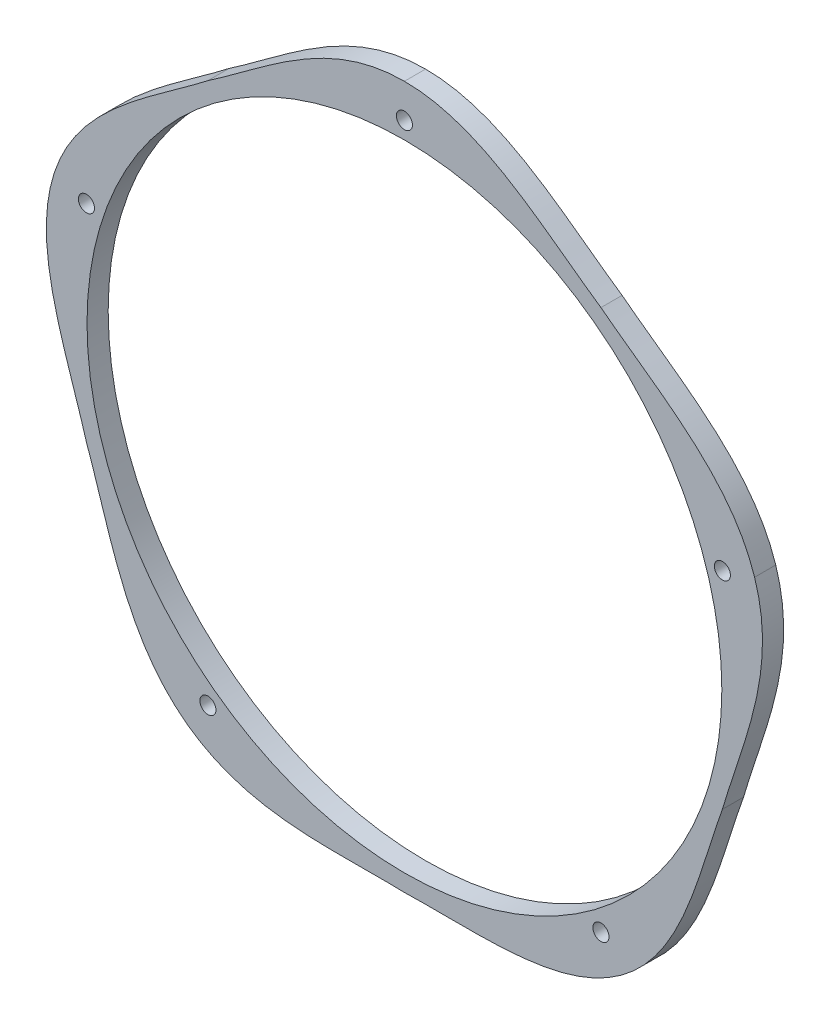
SolidWorks part; units mm, degrees
material "ABS"
ref_plane "Płaszczyzna przednia" through (0, 0, 0) normal (0, 0, 1) x (1, 0, 0)
ref_plane "Płaszczyzna górna" through (0, 0, 0) normal (0, 1, 0) x (1, 0, 0)
ref_plane "Płaszczyzna prawa" through (0, 0, 0) normal (1, 0, 0) x (0, 0, -1)
sketch "Szkic1" plane through (0, 0, 0) normal (0, 0, 1) x (1, 0, 0)
  line L0 (0, 0) -> (51.1373, 70.3845) construction
  line L1 (0, 0) -> (0, 87) construction
  line L2 (-1.4751, 37) -> (1.4751, 37)
  line L3 (-2.3701, 67) -> (2.3701, 67)
  line L4 (-6.4502, 41.5025) -> (-8.3403, 60.403)
  line L5 (6.4502, 41.5025) -> (8.3403, 60.403)
  line L6 (29.6563, 29.9183) -> (42.2948, 44.0981)
  line L7 (37.5075, 55.7306) -> (41.3424, 52.9445)
  line L8 (19.2195, 37.501) -> (28.7999, 53.9028)
  line L9 (20.5981, 30.9341) -> (22.9848, 29.2)
  line L10 (41.6213, 6.9063) -> (60.1808, 10.9493)
  line L11 (63.1452, 23.1741) -> (64.61, 18.6659)
  line L12 (37.6348, 19.1754) -> (55.0262, 26.8135)
  line L13 (34.8901, 13.0524) -> (35.8017, 10.2466)
  line L14 (37.7751, -18.7437) -> (55.1665, -26.3818)
  line L15 (64.7503, -18.2342) -> (63.2855, -22.7424)
  line L16 (41.7616, -6.4746) -> (60.321, -10.5176)
  line L17 (35.942, -9.8149) -> (35.0304, -12.6206)
  line L18 (19.5868, -37.2342) -> (29.1671, -53.6359)
  line L19 (41.7096, -52.6776) -> (37.8748, -55.4638)
  line L20 (30.0235, -29.6514) -> (42.662, -43.8313)
  line L21 (23.352, -28.9332) -> (20.9653, -30.6672)
  line L22 (-5.9963, -41.5025) -> (-7.8864, -60.403)
  line L23 (2.824, -67) -> (-1.9161, -67)
  line L24 (6.9042, -41.5025) -> (8.7942, -60.403)
  line L25 (1.929, -37) -> (-1.0211, -37)
  line L26 (-29.2023, -29.9183) -> (-41.8408, -44.0981)
  line L27 (-37.0536, -55.7306) -> (-40.8884, -52.9445)
  line L28 (-18.7656, -37.501) -> (-28.3459, -53.9028)
  line L29 (-20.1441, -30.9341) -> (-22.5308, -29.2)
  line L30 (-41.1673, -6.9063) -> (-59.7268, -10.9493)
  line L31 (-62.6913, -23.1741) -> (-64.1561, -18.6659)
  line L32 (-37.1809, -19.1754) -> (-54.5722, -26.8135)
  line L33 (-34.4362, -13.0524) -> (-35.3478, -10.2466)
  line L34 (-37.3211, 18.7437) -> (-54.7125, 26.3818)
  line L35 (-64.2963, 18.2342) -> (-62.8316, 22.7424)
  line L36 (-41.3076, 6.4746) -> (-59.8671, 10.5176)
  line L37 (-35.4881, 9.8149) -> (-34.5764, 12.6206)
  line L38 (-19.1328, 37.2342) -> (-28.7132, 53.6359)
  line L39 (-41.2557, 52.6776) -> (-37.4208, 55.4638)
  line L40 (-29.5696, 29.6514) -> (-42.2081, 43.8313)
  line L41 (-22.8981, 28.9332) -> (-20.5114, 30.6672)
  circle A0 centre (0, 0) radius 79 construction
  circle A2 centre (0, 0) radius 25 construction
  circle A3 centre (0, 0) radius 3.3
  circle A4 centre (0, 25) radius 3.2
  circle A5 centre (0, 79) radius 1.9
  circle A6 centre (25, 0) radius 3.2
  circle A7 centre (0, -25) radius 3.2
  circle A8 centre (-25, 0) radius 3.2
  circle A9 centre (75.1335, 24.4123) radius 1.9
  circle A10 centre (46.435, -63.9123) radius 1.9
  circle A11 centre (-46.435, -63.9123) radius 1.9
  circle A12 centre (-75.1335, 24.4123) radius 1.9
  circle A13 centre (0, 0) radius 87 construction
  arc A14 (8.3403, 60.403) -> (2.3701, 67) centre (2.3701, 61) ccw
  arc A15 (-2.3701, 67) -> (-8.3403, 60.403) centre (-2.3701, 61) ccw
  arc A16 (6.4502, 41.5025) -> (1.4751, 37) centre (1.4751, 42) cw
  arc A17 (-6.4502, 41.5025) -> (-1.4751, 37) centre (-1.4751, 42) ccw
  arc A18 (29.6563, 29.9183) -> (22.9848, 29.2) centre (25.9237, 33.2451) cw
  arc A19 (42.2948, 44.0981) -> (41.3424, 52.9445) centre (37.8157, 48.0904) ccw
  arc A20 (37.5075, 55.7306) -> (28.7999, 53.9028) centre (33.9808, 50.8765) ccw
  arc A21 (19.2195, 37.501) -> (20.5981, 30.9341) centre (23.537, 34.9791) ccw
  arc A22 (41.6213, 6.9063) -> (35.8017, 10.2466) centre (40.557, 11.7917) cw
  arc A23 (60.1808, 10.9493) -> (64.61, 18.6659) centre (58.9037, 16.8118) ccw
  arc A24 (63.1452, 23.1741) -> (55.0262, 26.8135) centre (57.4389, 21.32) ccw
  arc A25 (37.6348, 19.1754) -> (34.8901, 13.0524) centre (39.6454, 14.5974) ccw
  arc A26 (37.7751, -18.7437) -> (35.0304, -12.6206) centre (39.7857, -14.1657) cw
  arc A27 (55.1665, -26.3818) -> (63.2855, -22.7424) centre (57.5792, -20.8882) ccw
  arc A28 (64.7503, -18.2342) -> (60.321, -10.5176) centre (59.044, -16.3801) ccw
  arc A29 (41.7616, -6.4746) -> (35.942, -9.8149) centre (40.6973, -11.36) ccw
  arc A30 (19.5868, -37.2342) -> (20.9653, -30.6672) centre (23.9042, -34.7123) cw
  arc A31 (29.1671, -53.6359) -> (37.8748, -55.4638) centre (34.3481, -50.6097) ccw
  arc A32 (41.7096, -52.6776) -> (42.662, -43.8313) centre (38.1829, -47.8235) ccw
  arc A33 (30.0235, -29.6514) -> (23.352, -28.9332) centre (26.2909, -32.9783) ccw
  arc A34 (-5.9963, -41.5025) -> (-1.0211, -37) centre (-1.0211, -42) cw
  arc A35 (-7.8864, -60.403) -> (-1.9161, -67) centre (-1.9161, -61) ccw
  arc A36 (2.824, -67) -> (8.7942, -60.403) centre (2.824, -61) ccw
  arc A37 (6.9042, -41.5025) -> (1.929, -37) centre (1.929, -42) ccw
  arc A38 (-29.2023, -29.9183) -> (-22.5308, -29.2) centre (-25.4697, -33.2451) cw
  arc A39 (-41.8408, -44.0981) -> (-40.8884, -52.9445) centre (-37.3617, -48.0904) ccw
  arc A40 (-37.0536, -55.7306) -> (-28.3459, -53.9028) centre (-33.5269, -50.8765) ccw
  arc A41 (-18.7656, -37.501) -> (-20.1441, -30.9341) centre (-23.083, -34.9791) ccw
  arc A42 (-41.1673, -6.9063) -> (-35.3478, -10.2466) centre (-40.1031, -11.7917) cw
  arc A43 (-59.7268, -10.9493) -> (-64.1561, -18.6659) centre (-58.4497, -16.8118) ccw
  arc A44 (-62.6913, -23.1741) -> (-54.5722, -26.8135) centre (-56.9849, -21.32) ccw
  arc A45 (-37.1809, -19.1754) -> (-34.4362, -13.0524) centre (-39.1914, -14.5974) ccw
  arc A46 (-37.3211, 18.7437) -> (-34.5764, 12.6206) centre (-39.3317, 14.1657) cw
  arc A47 (-54.7125, 26.3818) -> (-62.8316, 22.7424) centre (-57.1252, 20.8882) ccw
  arc A48 (-64.2963, 18.2342) -> (-59.8671, 10.5176) centre (-58.59, 16.3801) ccw
  arc A49 (-41.3076, 6.4746) -> (-35.4881, 9.8149) centre (-40.2434, 11.36) ccw
  arc A50 (-19.1328, 37.2342) -> (-20.5114, 30.6672) centre (-23.4503, 34.7123) cw
  arc A51 (-28.7132, 53.6359) -> (-37.4208, 55.4638) centre (-33.8941, 50.6097) ccw
  arc A52 (-41.2557, 52.6776) -> (-42.2081, 43.8313) centre (-37.729, 47.8235) ccw
  arc A53 (-29.5696, 29.6514) -> (-22.8981, 28.9332) centre (-25.837, 32.9783) ccw
  spline S0 degree 3 poles (0, 87) (18.2248, 86.9986) (32.2889, 73.5369) (46.435, 63.9123) knots 0 0 0 0 1 1 1 1
  spline S1 degree 3 poles (82.7419, 26.8845) (77.1088, 44.2169) (59.9599, 53.4327) (46.435, 63.9123) knots 0 0 0 0 1 1 1 1
  spline S2 degree 3 poles (82.7419, 26.8845) (88.3724, 9.5512) (79.9156, -7.9844) (75.1335, -24.4123) knots 0 0 0 0 1 1 1 1
  spline S3 degree 3 poles (51.1373, -70.3845) (65.8807, -59.6711) (69.3462, -40.5137) (75.1335, -24.4123) knots 0 0 0 0 1 1 1 1
  spline S4 degree 3 poles (51.1373, -70.3845) (36.3923, -81.0957) (17.1016, -78.4715) (0, -79) knots 0 0 0 0 1 1 1 1
  spline S5 degree 3 poles (-51.1373, -70.3845) (-36.3923, -81.0957) (-17.1016, -78.4715) (0, -79) knots 0 0 0 0 1 1 1 1
  spline S6 degree 3 poles (-51.1373, -70.3845) (-65.8807, -59.6711) (-69.3462, -40.5137) (-75.1335, -24.4123) knots 0 0 0 0 1 1 1 1
  spline S7 degree 3 poles (-82.7419, 26.8845) (-88.3724, 9.5512) (-79.9156, -7.9844) (-75.1335, -24.4123) knots 0 0 0 0 1 1 1 1
  spline S8 degree 3 poles (-82.7419, 26.8845) (-77.1088, 44.2169) (-59.9599, 53.4327) (-46.435, 63.9123) knots 0 0 0 0 1 1 1 1
  spline S9 degree 3 poles (0, 87) (-18.2248, 86.9986) (-32.2889, 73.5369) (-46.435, 63.9123) knots 0 0 0 0 1 1 1 1
  point P18 (0, 0)
  point P27 (0, 0)
  point P43 (0, 37)
  point P64 (0, 0)
  point P65 (0, 67)
  point P67 (9, 67)
  point P70 (-9, 67)
  point P73 (6, 37)
  point P76 (-6, 37)
  point P188 (0.227, 0)
  dimension "D1" = 158
  dimension "D2" = 6.6
  dimension "D3" = 50
  dimension "D4" = 3.8
  dimension "D5" = 6.4
  dimension "D8" = 174
  dimension "D13" = 37
  dimension "D14" = 6
  dimension "D15" = 5
  dimension "D9" = 36
  dimension "D10" = 12
  dimension "D11" = 18
  dimension "D12" = 30
  dimension "D6" = 4
  dimension "D7" = 5
  dimension "D16" = 10
extrude "Dodanie-wyciągnięcie1" add sketch "Szkic1" along normal blind 5 contours S0 S9 S8 S7 S6 S5 S4 S3 S2 S1 A3 A4 A5 A6 A7 A8 A9 A10 A11 A12 A17 L4 A15 L3 A14 L5 A16 L2 A21 L8 A20 L7 A19 L6 A18 L9 A25 L12 region at (23.5794, 77.0008, 0)
sketch "Szkic2" plane through (0, 0, 5) normal (0, 0, 1) x (1, 0, 0)
  circle A0 centre (0, 0) radius 75
  circle A1 centre (0, 25) radius 6 construction
  circle A2 centre (25, 0) radius 6 construction
  circle A3 centre (0, -25) radius 6 construction
  circle A4 centre (-25, 0) radius 6 construction
  circle A5 centre (0, 0) radius 32.5 construction
  point P14 (0, 0)
  point P32 (0, 0)
  dimension "D1" = 150
  dimension "D2" = 12
  dimension "D3" = 4
  dimension "D4" = 65
extrude "Wytnij-wyciągnięcie1" cut sketch "Szkic2" against normal blind 5.5 contours A0 region at (0, 0, 5)
